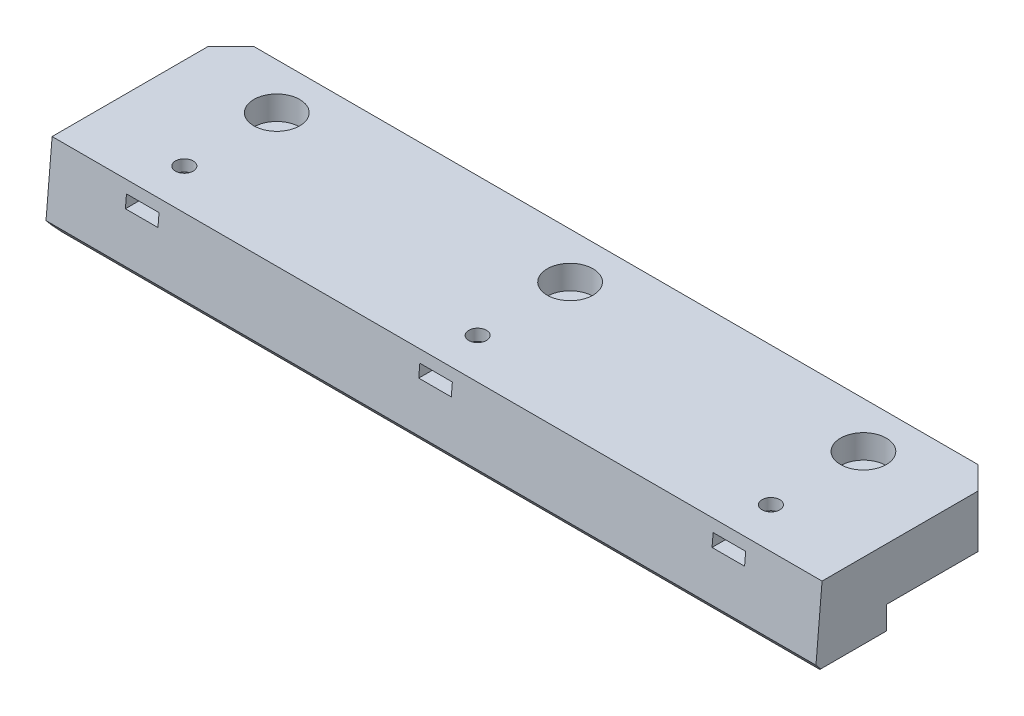
SolidWorks part; units mm, degrees
material "PET"
ref_plane "Front Plane" through (0, 0, 0) normal (0, 0, 1) x (1, 0, 0)
ref_plane "Top Plane" through (0, 0, 0) normal (0, 1, 0) x (1, 0, 0)
ref_plane "Right Plane" through (0, 0, 0) normal (1, 0, 0) x (0, 0, -1)
sketch "Sketch1" plane through (0, 0, 0) normal (1, 0, 0) x (0, 0, -1)
  line L1 (12.7, -4.7625) -> (-12.7, -4.7625)
  line L2 (12.7, -4.7625) -> (12.7, 4.7625)
  line L3 (12.7, 4.7625) -> (-12.7, 4.7625)
  line L4 (-12.7, -4.7625) -> (-12.7, 4.7625)
  line L5 (12.7, -4.7625) -> (-12.7, 4.7625) construction
  line L6 (12.7, 4.7625) -> (-12.7, -4.7625) construction
  point P0 (0, 0)
  dimension "D1" = 9.525
  dimension "D2" = 25.4
extrude "Boss-Extrude1" add sketch "Sketch1" along normal mid plane 213.36
sketch "Sketch2" plane through (-106.68, 0, 0) normal (-1, 0, 0) x (0, 0, 1)
  line L0 (12.7, 4.7625) -> (37.438, 4.7625)
  line L1 (12.7, 4.7625) -> (12.7, -4.7625) construction
  line L2 (37.438, 4.7625) -> (38.829, -11.1363)
  line L4 (38.829, -11.1363) -> (12.7, -11.1363)
  line L9 (12.7, -11.1363) -> (12.7, 4.7625)
  line L10 (-12.7, 4.7625) -> (12.7, 4.7625) construction
  line L11 (25.5674, 149.1875) -> (39.494, -9.9944) construction
  line L12 (19.05, -11.1363) -> (38.1, -11.1363) construction
  dimension "D1" = 0.762
extrude "Boss-Extrude2" add sketch "Sketch2" against normal through all
chamfer "Chamfer1" distance 6.35 angle 45 4 edges at (106.68, -7.9494, 12.7) (106.68, 0, -12.7) (-106.68, 0, -12.7) (-106.68, -7.9494, 12.7)
chamfer "Chamfer2" distance 3.175 angle 45 1 edges at (0, -11.1363, 38.829) first distance on face at (0, -3.1869, 38.1335)
hole_wizard "#8 Clearance Hole1" positions "Sketch3" profile "Sketch4" hole size "#8" standard "ANSI Inch" end condition up to next
sketch "Sketch3" plane through (0, -11.1363, 0) normal (0, -1, 0) x (-1, 0, 0)
  line L0 (0, -38.5523) -> (0, -12.7) construction
  line L1 (106.68, -38.5523) -> (-106.68, -38.5523) construction
  line L2 (-100.33, -12.7) -> (100.33, -12.7) construction
  line L3 (0, -12.7) -> (0, 12.7) construction
  line L4 (-100.33, 12.7) -> (100.33, 12.7) construction
  line L6 (0, 0) -> (106.68, 0) construction
  line L7 (106.68, -19.05) -> (106.68, 6.35) construction
  line L9 (0, -25.6261) -> (106.68, -25.6261) construction
  line L10 (106.68, -19.05) -> (106.68, -35.8983) construction
  point P12 (0, 0)
  point P19 (0, -25.6261)
  point P24 (81.28, -25.6261)
  point P26 (81.28, 0)
  point P35 (-81.28, 0)
  point P36 (-81.28, -25.6261)
  dimension "D1" = 25.4
sketch "Sketch4" plane through (81.28, -11.1363, 25.6261) normal (1, 0, 0) x (0, 0, -1)
  line L0 (0, 0) -> (0, 15.8988)
  line L1 (0, 15.8988) -> (2.4574, 15.8988)
  line L2 (2.4574, 15.8988) -> (2.4574, 0)
  line L5 (2.4574, 0) -> (0, 0)
  line L11 (0, -6.35) -> (0, 107.95) construction
  dimension "Thru Hole Dia." = 4.9149
  dimension "Thru Hole Depth" = 15.8988
chamfer "Chamfer3" distance 1.5875 angle 45 10 edges at (-106.68, -4.7625, 6.35) (-103.505, -4.7625, -9.525) (0, -4.7625, -12.7) (103.505, -4.7625, -9.525) (106.68, -4.7625, 6.35) (106.68, -11.1363, 27.4741) (103.505, -11.1363, 15.875) (0, -11.1363, 12.7) (-103.505, -11.1363, 15.875) (-106.68, -11.1363, 27.4741)
sketch "Sketch5" plane through (0, 4.7625, 0) normal (0, 1, 0) x (1, 0, 0)
  line L0 (106.68, 6.35) -> (106.68, -37.438) construction
  line L1 (85.7885, -37.438) -> (85.7885, -23.0232)
  line L2 (85.7885, -23.0232) -> (81.28, -20.4202)
  line L3 (81.28, -20.4202) -> (76.7715, -23.0232)
  line L4 (76.7715, -23.0232) -> (76.7715, -37.438)
  line L20 (73.5965, -37.438) -> (76.7715, -37.438)
  line L21 (73.5965, -37.438) -> (73.5965, -17.2452)
  line L22 (73.5965, -17.2452) -> (88.9635, -17.2452)
  line L23 (88.9635, -37.438) -> (88.9635, -17.2452)
  line L24 (76.7715, -28.2291) -> (81.28, -30.8321) [skipped]
  line L25 (81.28, -30.8321) -> (85.7885, -28.2291) [skipped]
  line L26 (85.7885, -37.438) -> (88.9635, -37.438)
  line L27 (81.28, -20.4202) -> (81.28, -17.2452) construction
  line L28 (4.5085, -37.438) -> (4.5085, -23.0232)
  line L29 (4.5085, -23.0232) -> (0, -20.4202)
  line L30 (0, -20.4202) -> (-4.5085, -23.0232)
  line L31 (-4.5085, -23.0232) -> (-4.5085, -37.438)
  line L32 (-7.6835, -37.438) -> (-4.5085, -37.438)
  line L33 (-7.6835, -37.438) -> (-7.6835, -17.2452)
  line L34 (-7.6835, -17.2452) -> (7.6835, -17.2452)
  line L35 (7.6835, -37.438) -> (7.6835, -17.2452)
  line L36 (4.5085, -37.438) -> (7.6835, -37.438)
  line L37 (0, -20.4202) -> (0, -17.2452) construction
  line L38 (-76.7715, -37.438) -> (-76.7715, -23.0232)
  line L39 (-76.7715, -23.0232) -> (-81.28, -20.4202)
  line L40 (-81.28, -20.4202) -> (-85.7885, -23.0232)
  line L41 (-85.7885, -23.0232) -> (-85.7885, -37.438)
  line L42 (-88.9635, -37.438) -> (-85.7885, -37.438)
  line L43 (-88.9635, -37.438) -> (-88.9635, -17.2452)
  line L44 (-88.9635, -17.2452) -> (-73.5965, -17.2452)
  line L45 (-73.5965, -37.438) -> (-73.5965, -17.2452)
  line L46 (-76.7715, -37.438) -> (-73.5965, -37.438)
  line L47 (-81.28, -20.4202) -> (-81.28, -17.2452) construction
  line L48 (85.7885, -37.438) -> (4.5085, -37.438) construction
  line L49 (106.68, -37.438) -> (-106.68, -37.438) construction
  circle A0 centre (81.28, -25.6261) radius 4.5085 construction
  circle A1 centre (0, -25.6261) radius 4.5085 construction
  circle A2 centre (-81.28, -25.6261) radius 4.5085 construction
  dimension "D1" = 9.017
  dimension "D2" = 3.175
  dimension "D3" = 3
  dimension "D4" = 81.28
  dimension "D5" = 0
extrude "Boss-Extrude3" add sketch "Sketch5" along normal blind 3.429
sketch "Sketch6" plane through (0, 8.1915, 0) normal (0, 1, 0) x (1, 0, 0)
  line L1 (-88.9635, -17.2452) -> (-73.5965, -17.2452)
  line L2 (-88.9635, -17.2452) -> (-88.9635, -37.438)
  line L3 (-88.9635, -37.438) -> (-73.5965, -37.438)
  line L4 (-73.5965, -17.2452) -> (-73.5965, -37.438)
  line L5 (-7.6835, -17.2452) -> (7.6835, -17.2452)
  line L6 (-7.6835, -17.2452) -> (-7.6835, -37.438)
  line L7 (-7.6835, -37.438) -> (7.6835, -37.438)
  line L8 (7.6835, -17.2452) -> (7.6835, -37.438)
  line L9 (73.5965, -17.2452) -> (88.9635, -17.2452)
  line L10 (73.5965, -17.2452) -> (73.5965, -37.438)
  line L11 (73.5965, -37.438) -> (88.9635, -37.438)
  line L12 (88.9635, -17.2452) -> (88.9635, -37.438)
  circle A0 centre (81.28, -25.6261) radius 2.4574 construction
  circle A1 centre (0, -25.6261) radius 2.4574 construction
  circle A2 centre (-81.28, -25.6261) radius 2.4574 construction
  circle A3 centre (81.28, -25.6261) radius 2.4574
  circle A4 centre (0, -25.6261) radius 2.4574
  circle A5 centre (-81.28, -25.6261) radius 2.4574
extrude "Boss-Extrude4" add sketch "Sketch6" along normal blind 3.175
chamfer "Chamfer4" [suppressed] distance 6.604 angle 45
sketch "Sketch7" plane through (0, 4.7625, 0) normal (0, 1, 0) x (1, 0, 0)
  line L44 (-73.5965, -17.2452) -> (-73.5965, -37.438)
  line L45 (-73.5965, -37.438) -> (-7.6835, -37.438)
  line L47 (-7.6835, -37.438) -> (-7.6835, -17.2452)
  line L49 (-7.6835, -17.2452) -> (7.6835, -17.2452)
  line L50 (7.6835, -17.2452) -> (7.6835, -37.438)
  line L51 (7.6835, -37.438) -> (73.5965, -37.438)
  line L52 (73.5965, -37.438) -> (73.5965, -17.2452)
  line L53 (73.5965, -17.2452) -> (88.9635, -17.2452)
  line L54 (88.9635, -17.2452) -> (88.9635, -37.438)
  line L55 (88.9635, -37.438) -> (106.68, -37.438)
  line L56 (106.68, -37.438) -> (106.68, 6.35)
  line L57 (106.68, 6.35) -> (100.33, 12.7)
  line L58 (100.33, 12.7) -> (-100.33, 12.7)
  line L59 (-100.33, 12.7) -> (-106.68, 6.35)
  line L60 (-106.68, 6.35) -> (-106.68, -37.438)
  line L61 (-106.68, -37.438) -> (-88.9635, -37.438)
  line L62 (-88.9635, -37.438) -> (-88.9635, -17.2452)
  line L63 (-88.9635, -17.2452) -> (-73.5965, -17.2452)
  line L64 (-73.5965, -17.2452) -> (-73.5965, -37.438)
  line L65 (-73.5965, -37.438) -> (-7.6835, -37.438)
  line L66 (-7.6835, -37.438) -> (-7.6835, -17.2452)
  line L67 (-7.6835, -17.2452) -> (7.6835, -17.2452)
  line L68 (7.6835, -17.2452) -> (7.6835, -37.438)
  line L69 (7.6835, -37.438) -> (73.5965, -37.438)
  line L70 (73.5965, -37.438) -> (73.5965, -17.2452)
  line L71 (73.5965, -17.2452) -> (88.9635, -17.2452)
  line L72 (88.9635, -17.2452) -> (88.9635, -37.438)
  line L73 (88.9635, -37.438) -> (106.68, -37.438)
  line L74 (106.68, -37.438) -> (106.68, 6.35)
  line L75 (106.68, 6.35) -> (100.33, 12.7)
  line L76 (100.33, 12.7) -> (-100.33, 12.7)
  line L77 (-100.33, 12.7) -> (-106.68, 6.35)
  line L78 (-106.68, 6.35) -> (-106.68, -37.438)
  line L79 (-106.68, -37.438) -> (-88.9635, -37.438)
  line L80 (-88.9635, -37.438) -> (-88.9635, -17.2452)
  line L81 (-88.9635, -17.2452) -> (-73.5965, -17.2452)
  circle A0 centre (81.28, 0) radius 6.35
  circle A1 centre (0, 0) radius 6.35
  circle A2 centre (-81.28, 0) radius 6.35
  dimension "D5" = 12.7
  dimension "D1" = 0
extrude "Boss-Extrude5" add sketch "Sketch7" along normal up to surface (6.604 mm away) up to face at (81.28, 11.3665, 27.3416)
sketch "Sketch8" plane through (-106.68, 0, 0) normal (-1, 0, 0) x (0, 0, 1)
  line L0 (37.438, 4.7625) -> (36.8603, 11.3665)
  line L2 (36.8603, 11.3665) -> (37.438, 11.3665)
  line L3 (37.438, 11.3665) -> (37.438, 4.7625)
  line L4 (38.5523, -7.9734) -> (37.438, 4.7625) construction
  line L5 (-6.35, 11.3665) -> (37.438, 11.3665) construction
extrude "Cut-Extrude1" cut sketch "Sketch8" against normal through all
